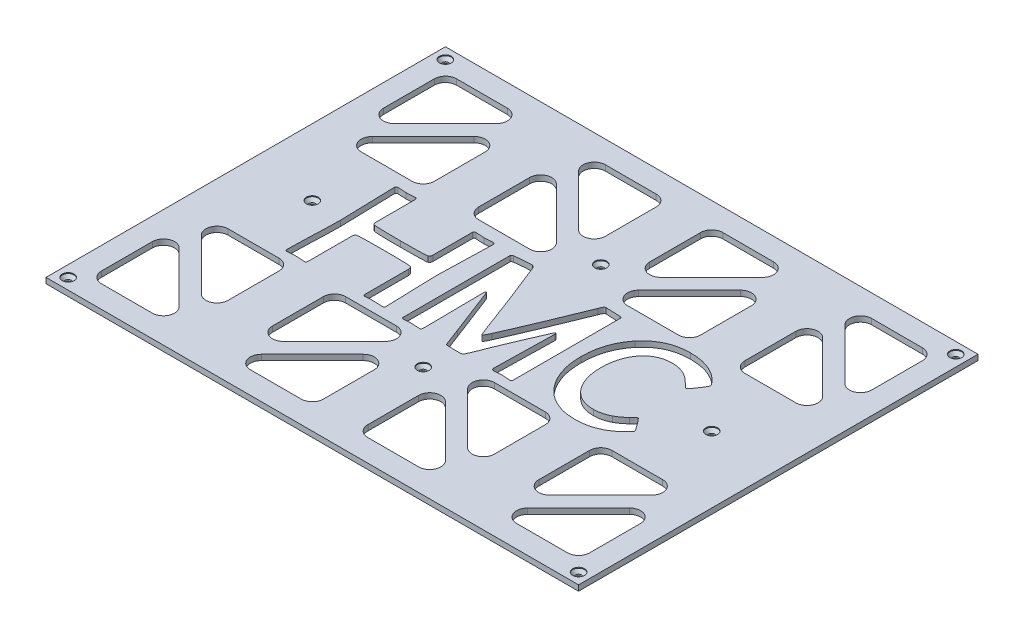
SolidWorks part; units mm, degrees
material "1060 Alloy"
ref_plane "Front Plane" through (0, 0, 0) normal (0, 0, 1) x (1, 0, 0)
ref_plane "Top Plane" through (0, 0, 0) normal (0, 1, 0) x (1, 0, 0)
ref_plane "Right Plane" through (0, 0, 0) normal (1, 0, 0) x (0, 0, -1)
sketch "Sketch2" plane through (0, 0, 0) normal (0, 1, 0) x (1, 0, 0)
  line L0 (-240.3287, 78.4637) -> (-240.3287, 20.2243)
  line L1 (-265.7287, 116.5637) -> (343.8713, 116.5637)
  line L2 (-265.7287, 116.5637) -> (-265.7287, -340.6363)
  line L3 (-265.7287, -340.6363) -> (343.8713, -340.6363)
  line L4 (343.8713, 116.5637) -> (343.8713, -340.6363)
  line L5 (-218.6484, 11.244) -> (-160.4089, 69.4835)
  line L6 (-169.3892, 91.1637) -> (-227.6287, 91.1637)
  line L7 (-218.6484, -14.156) -> (-160.4089, 44.0835)
  line L8 (-138.7287, 35.1032) -> (-138.7287, -23.1363)
  line L9 (-151.4287, -35.8363) -> (-209.6682, -35.8363)
  line L10 (39.0713, 116.5637) -> (39.0713, -340.6363) construction
  line L11 (343.8713, -112.0363) -> (-265.7287, -112.0363) construction
  line L12 (-113.3287, 116.5637) -> (-113.3287, -340.6363) construction
  line L13 (-75.2287, -35.8363) -> (-16.9892, -35.8363)
  line L14 (-87.9287, 35.1032) -> (-87.9287, -23.1363)
  line L15 (-8.0089, -14.156) -> (-66.2484, 44.0835)
  line L16 (-57.2682, 91.1637) -> (0.9713, 91.1637)
  line L17 (-8.0089, 11.244) -> (-66.2484, 69.4835)
  line L18 (13.6713, 78.4637) -> (13.6713, 20.2243)
  line L19 (64.4713, 78.4637) -> (64.4713, 20.2243)
  line L20 (86.1516, 11.244) -> (144.3911, 69.4835)
  line L21 (135.4108, 91.1637) -> (77.1713, 91.1637)
  line L22 (86.1516, -14.156) -> (144.3911, 44.0835)
  line L23 (166.0713, 35.1032) -> (166.0713, -23.1363)
  line L24 (153.3713, -35.8363) -> (95.1318, -35.8363)
  line L25 (229.5713, -35.8363) -> (287.8108, -35.8363)
  line L26 (216.8713, 35.1032) -> (216.8713, -23.1363)
  line L27 (296.7911, -14.156) -> (238.5516, 44.0835)
  line L28 (247.5318, 91.1637) -> (305.7713, 91.1637)
  line L29 (296.7911, 11.244) -> (238.5516, 69.4835)
  line L30 (318.4713, 78.4637) -> (318.4713, 20.2243)
  line L31 (318.4713, -302.5363) -> (318.4713, -244.2968)
  line L32 (296.7911, -235.3165) -> (238.5516, -293.556)
  line L33 (247.5318, -315.2363) -> (305.7713, -315.2363)
  line L34 (296.7911, -209.9165) -> (238.5516, -268.156)
  line L35 (216.8713, -259.1757) -> (216.8713, -200.9363)
  line L36 (229.5713, -188.2363) -> (287.8108, -188.2363)
  line L37 (153.3713, -188.2363) -> (95.1318, -188.2363)
  line L38 (166.0713, -259.1757) -> (166.0713, -200.9363)
  line L39 (86.1516, -209.9165) -> (144.3911, -268.156)
  line L40 (135.4108, -315.2363) -> (77.1713, -315.2363)
  line L41 (86.1516, -235.3165) -> (144.3911, -293.556)
  line L42 (64.4713, -302.5363) -> (64.4713, -244.2968)
  line L43 (13.6713, -302.5363) -> (13.6713, -244.2968)
  line L44 (-8.0089, -235.3165) -> (-66.2484, -293.556)
  line L45 (-57.2682, -315.2363) -> (0.9713, -315.2363)
  line L46 (-8.0089, -209.9165) -> (-66.2484, -268.156)
  line L47 (-87.9287, -259.1757) -> (-87.9287, -200.9363)
  line L48 (-75.2287, -188.2363) -> (-16.9892, -188.2363)
  line L49 (-151.4287, -188.2363) -> (-209.6682, -188.2363)
  line L50 (-138.7287, -259.1757) -> (-138.7287, -200.9363)
  line L51 (-218.6484, -209.9165) -> (-160.4089, -268.156)
  line L52 (-169.3892, -315.2363) -> (-227.6287, -315.2363)
  line L53 (-218.6484, -235.3165) -> (-160.4089, -293.556)
  line L54 (-240.3287, -302.5363) -> (-240.3287, -244.2968)
  arc A0 (-160.4089, 44.0835) -> (-138.7287, 35.1032) centre (-151.4287, 35.1032) cw
  arc A1 (-138.7287, -23.1363) -> (-151.4287, -35.8363) centre (-151.4287, -23.1363) cw
  arc A2 (-218.6484, -14.156) -> (-209.6682, -35.8363) centre (-209.6682, -23.1363) ccw
  arc A3 (-240.3287, 20.2243) -> (-218.6484, 11.244) centre (-227.6287, 20.2243) ccw
  arc A4 (-160.4089, 69.4835) -> (-169.3892, 91.1637) centre (-169.3892, 78.4637) ccw
  arc A5 (-240.3287, 78.4637) -> (-227.6287, 91.1637) centre (-227.6287, 78.4637) cw
  arc A6 (13.6713, 78.4637) -> (0.9713, 91.1637) centre (0.9713, 78.4637) ccw
  arc A7 (-66.2484, 69.4835) -> (-57.2682, 91.1637) centre (-57.2682, 78.4637) cw
  arc A8 (13.6713, 20.2243) -> (-8.0089, 11.244) centre (0.9713, 20.2243) cw
  arc A9 (-8.0089, -14.156) -> (-16.9892, -35.8363) centre (-16.9892, -23.1363) cw
  arc A10 (-87.9287, -23.1363) -> (-75.2287, -35.8363) centre (-75.2287, -23.1363) ccw
  arc A11 (-66.2484, 44.0835) -> (-87.9287, 35.1032) centre (-75.2287, 35.1032) ccw
  arc A12 (144.3911, 44.0835) -> (166.0713, 35.1032) centre (153.3713, 35.1032) cw
  arc A13 (166.0713, -23.1363) -> (153.3713, -35.8363) centre (153.3713, -23.1363) cw
  arc A14 (86.1516, -14.156) -> (95.1318, -35.8363) centre (95.1318, -23.1363) ccw
  arc A15 (64.4713, 20.2243) -> (86.1516, 11.244) centre (77.1713, 20.2243) ccw
  arc A16 (144.3911, 69.4835) -> (135.4108, 91.1637) centre (135.4108, 78.4637) ccw
  arc A17 (64.4713, 78.4637) -> (77.1713, 91.1637) centre (77.1713, 78.4637) cw
  arc A18 (318.4713, 78.4637) -> (305.7713, 91.1637) centre (305.7713, 78.4637) ccw
  arc A19 (238.5516, 69.4835) -> (247.5318, 91.1637) centre (247.5318, 78.4637) cw
  arc A20 (318.4713, 20.2243) -> (296.7911, 11.244) centre (305.7713, 20.2243) cw
  arc A21 (296.7911, -14.156) -> (287.8108, -35.8363) centre (287.8108, -23.1363) cw
  arc A22 (216.8713, -23.1363) -> (229.5713, -35.8363) centre (229.5713, -23.1363) ccw
  arc A23 (238.5516, 44.0835) -> (216.8713, 35.1032) centre (229.5713, 35.1032) ccw
  arc A24 (238.5516, -268.156) -> (216.8713, -259.1757) centre (229.5713, -259.1757) cw
  arc A25 (216.8713, -200.9363) -> (229.5713, -188.2363) centre (229.5713, -200.9363) cw
  arc A26 (296.7911, -209.9165) -> (287.8108, -188.2363) centre (287.8108, -200.9363) ccw
  arc A27 (318.4713, -244.2968) -> (296.7911, -235.3165) centre (305.7713, -244.2968) ccw
  arc A28 (238.5516, -293.556) -> (247.5318, -315.2363) centre (247.5318, -302.5363) ccw
  arc A29 (318.4713, -302.5363) -> (305.7713, -315.2363) centre (305.7713, -302.5363) cw
  arc A30 (64.4713, -302.5363) -> (77.1713, -315.2363) centre (77.1713, -302.5363) ccw
  arc A31 (144.3911, -293.556) -> (135.4108, -315.2363) centre (135.4108, -302.5363) cw
  arc A32 (64.4713, -244.2968) -> (86.1516, -235.3165) centre (77.1713, -244.2968) cw
  arc A33 (86.1516, -209.9165) -> (95.1318, -188.2363) centre (95.1318, -200.9363) cw
  arc A34 (166.0713, -200.9363) -> (153.3713, -188.2363) centre (153.3713, -200.9363) ccw
  arc A35 (144.3911, -268.156) -> (166.0713, -259.1757) centre (153.3713, -259.1757) ccw
  arc A36 (-66.2484, -268.156) -> (-87.9287, -259.1757) centre (-75.2287, -259.1757) cw
  arc A37 (-87.9287, -200.9363) -> (-75.2287, -188.2363) centre (-75.2287, -200.9363) cw
  arc A38 (-8.0089, -209.9165) -> (-16.9892, -188.2363) centre (-16.9892, -200.9363) ccw
  arc A39 (13.6713, -244.2968) -> (-8.0089, -235.3165) centre (0.9713, -244.2968) ccw
  arc A40 (-66.2484, -293.556) -> (-57.2682, -315.2363) centre (-57.2682, -302.5363) ccw
  arc A41 (13.6713, -302.5363) -> (0.9713, -315.2363) centre (0.9713, -302.5363) cw
  arc A42 (-240.3287, -302.5363) -> (-227.6287, -315.2363) centre (-227.6287, -302.5363) ccw
  arc A43 (-160.4089, -293.556) -> (-169.3892, -315.2363) centre (-169.3892, -302.5363) cw
  arc A44 (-240.3287, -244.2968) -> (-218.6484, -235.3165) centre (-227.6287, -244.2968) cw
  arc A45 (-218.6484, -209.9165) -> (-209.6682, -188.2363) centre (-209.6682, -200.9363) cw
  arc A46 (-138.7287, -200.9363) -> (-151.4287, -188.2363) centre (-151.4287, -200.9363) ccw
  arc A47 (-160.4089, -268.156) -> (-138.7287, -259.1757) centre (-151.4287, -259.1757) ccw
  text T0 "HMC" font "Berlin Sans FB" height 127
  point P19 (-138.7287, 65.7637)
  point P22 (-138.7287, -35.8363)
  point P25 (-240.3287, -35.8363)
  point P28 (-240.3287, -10.4363)
  point P31 (-138.7287, 91.1637)
  point P34 (-240.3287, 91.1637)
  point P53 (13.6713, 91.1637)
  point P54 (-87.9287, 91.1637)
  point P55 (13.6713, -10.4363)
  point P56 (13.6713, -35.8363)
  point P57 (-87.9287, -35.8363)
  point P58 (-87.9287, 65.7637)
  point P95 (166.0713, 65.7637)
  point P96 (166.0713, -35.8363)
  point P97 (64.4713, -35.8363)
  point P98 (64.4713, -10.4363)
  point P99 (166.0713, 91.1637)
  point P100 (64.4713, 91.1637)
  point P101 (318.4713, 91.1637)
  point P102 (216.8713, 91.1637)
  point P103 (318.4713, -10.4363)
  point P104 (318.4713, -35.8363)
  point P105 (216.8713, -35.8363)
  point P106 (216.8713, 65.7637)
  point P179 (216.8713, -289.8363)
  point P180 (216.8713, -188.2363)
  point P181 (318.4713, -188.2363)
  point P182 (318.4713, -213.6363)
  point P183 (216.8713, -315.2363)
  point P184 (318.4713, -315.2363)
  point P185 (64.4713, -315.2363)
  point P186 (166.0713, -315.2363)
  point P187 (64.4713, -213.6363)
  point P188 (64.4713, -188.2363)
  point P189 (166.0713, -188.2363)
  point P190 (166.0713, -289.8363)
  point P191 (-87.9287, -289.8363)
  point P192 (-87.9287, -188.2363)
  point P193 (13.6713, -188.2363)
  point P194 (13.6713, -213.6363)
  point P195 (-87.9287, -315.2363)
  point P196 (13.6713, -315.2363)
  point P197 (-240.3287, -315.2363)
  point P198 (-138.7287, -315.2363)
  point P199 (-240.3287, -213.6363)
  point P200 (-240.3287, -188.2363)
  point P201 (-138.7287, -188.2363)
  point P202 (-138.7287, -289.8363)
  dimension "D11" = 12.7
  dimension "D1" = 609.6
  dimension "D2" = 457.2
  dimension "D3" = 25.4
  dimension "D4" = 25.4
  dimension "D5" = 101.6
  dimension "D6" = 101.6
  dimension "D7" = 101.6
  dimension "D8" = 101.6
  dimension "D9" = 25.4
  dimension "D10" = 152.4
extrude "Boss-Extrude1" add sketch "Sketch2" along normal blind 6.35
sketch "Sketch3" plane through (0, 6.35, 0) normal (0, 1, 0) x (1, 0, 0)
  line L0 (-265.7287, 116.5637) -> (-265.7287, -340.6363) construction
  line L1 (343.8713, -340.6363) -> (343.8713, 116.5637) construction
  line L2 (343.8713, 116.5637) -> (-265.7287, 116.5637) construction
  line L3 (-265.7287, -340.6363) -> (343.8713, -340.6363) construction
  line L4 (343.8713, -340.6363) -> (343.8713, 116.5637) construction
  point P0 (39.0713, -10.4363)
  point P1 (39.0713, -213.6363)
  point P2 (267.6713, -112.0363)
  point P3 (-189.5287, -112.0363)
  point P4 (-265.7287, -112.0363)
  point P9 (39.0713, 116.5637)
  point P14 (-253.0287, -327.9363)
  point P15 (331.1713, -327.9363)
  point P16 (331.1713, 103.8637)
  point P17 (-253.0287, 103.8637)
  dimension "D1" = 76.2
  dimension "D2" = 76.2
  dimension "D3" = 127
  dimension "D4" = 127
  dimension "D5" = 12.7
  dimension "D6" = 12.7
  dimension "D7" = 12.7
  dimension "D8" = 12.7
  dimension "D9" = 12.7
  dimension "D10" = 12.7
  dimension "D11" = 12.7
  dimension "D12" = 12.7
hole_wizard "CSK for 1/4 Flat Head Socket Cap Screw1" positions "3DSketch1" profile "Sketch5" countersink size "1/4" standard "ANSI Inch" end condition through all
sketch3d "3DSketch1"
  point P0 (-253.0287, 6.35, -103.8637)
  point P3 (-189.5287, 6.35, 112.0363)
  point P6 (-253.0287, 6.35, 327.9363)
  point P9 (39.0713, 6.35, 213.6363)
  point P12 (39.0713, 6.35, 10.4363)
  point P15 (331.1713, 6.35, -103.8637)
  point P18 (267.6713, 6.35, 112.0363)
  point P21 (331.1713, 6.35, 327.9363)
sketch "Sketch5" plane through (-253.0287, 6.35, -103.8637) normal (1, 0, 0) x (0, 0, 1)
  line L0 (0, 0) -> (0, 6.35)
  line L1 (0, 6.35) -> (3.5712, 6.35)
  line L2 (3.5712, 6.35) -> (3.5712, 4.6655)
  line L3 (3.5712, 4.6655) -> (6.7437, 1.016)
  line L4 (6.7437, 1.016) -> (6.7437, 0)
  line L6 (6.7437, 0) -> (0, 0)
  line L7 (-3.5712, 4.6655) -> (-6.7437, 1.016) construction
  line L11 (0, -6.35) -> (0, 107.95) construction
  dimension "Thru Hole Dia." = 7.1425
  dimension "Thru Hole Depth" = 6.35
  dimension "C'Sink Dia." = 13.4874
  dimension "C'Sink Angle" = 82
  dimension "Head Clearance" = 1.016
